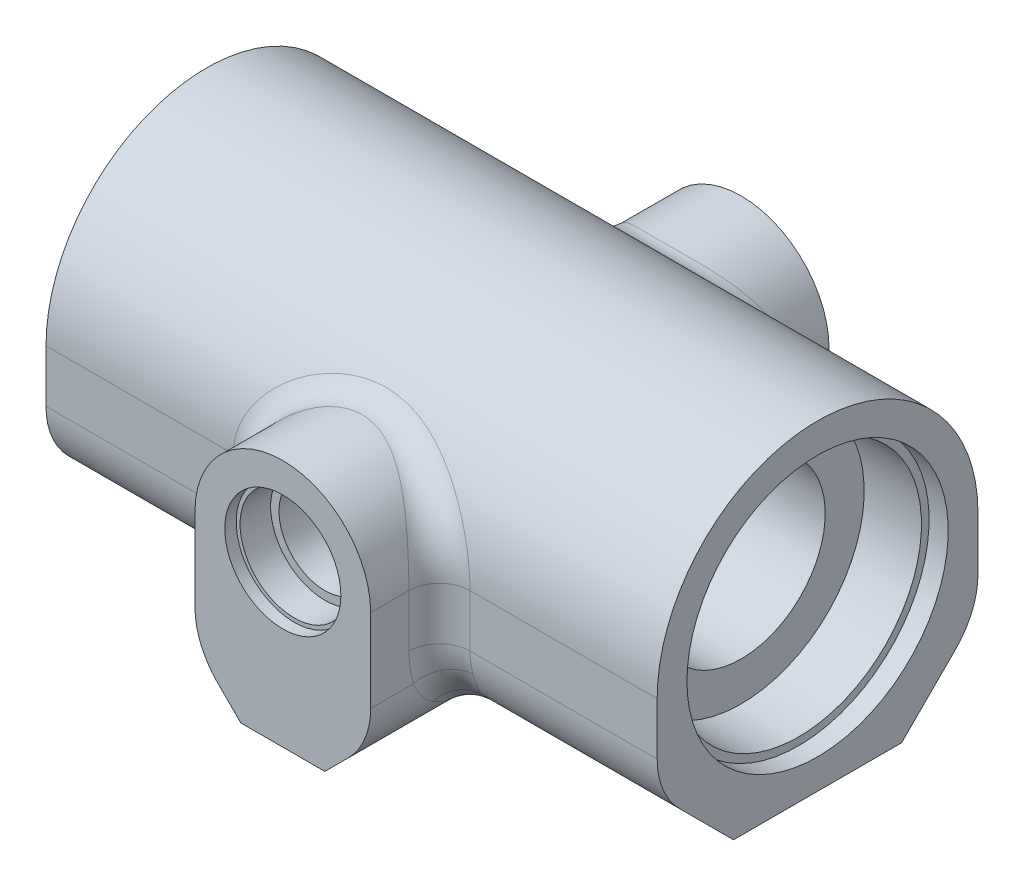
SolidWorks part; units mm, degrees
ref_plane "Front Plane" through (0, 0, 0) normal (0, 0, 1) x (1, 0, 0)
ref_plane "Top Plane" through (0, 0, 0) normal (0, 1, 0) x (1, 0, 0)
ref_plane "Right Plane" through (0, 0, 0) normal (1, 0, 0) x (0, 0, -1)
sketch "Sketch3" plane through (0, 0, 0) normal (1, 0, 0) x (0, 0, -1)
  line L3 (-21, 0) -> (-21, -21)
  line L4 (-21, -21) -> (21, -21)
  line L5 (21, -21) -> (21, 0)
  arc A1 (21, 0) -> (-21, 0) centre (0, 0) ccw
  arc A2 (-21, 0) -> (0, -21) centre (0, 0) ccw construction
  arc A3 (0, -21) -> (21, 0) centre (0, 0) ccw construction
  dimension "D1" = 42
extrude "Boss-Extrude1" add sketch "Sketch3" along normal mid plane 80
sketch "Sketch4" plane through (0, 0, 0) normal (0, 0, 1) x (1, 0, 0)
  line L0 (-11.5, 0) -> (-11.5, -21)
  line L1 (-11.5, -21) -> (11.5, -21)
  line L2 (11.5, -21) -> (11.5, 0)
  line L3 (0, 0) -> (26.2148, 0) construction
  arc A0 (11.5, 0) -> (-11.5, 0) centre (0, 0) ccw
  arc A1 (-11.5, 0) -> (11.5, 0) centre (0, 0) ccw construction
  dimension "D1" = 23
  dimension "D2" = 42
extrude "Boss-Extrude2" add sketch "Sketch4" along normal mid plane 60
chamfer "Chamfer1" distance 10 angle 45 4 edges at (25.75, -21, -21) (25.75, -21, 21) (-25.75, -21, -21) (-25.75, -21, 21)
fillet "Fillet1" radius 10 4 edges at (25.75, -11, 21) (25.75, -11, -21) (-25.75, -11, -21) (-25.75, -11, 21)
chamfer "Chamfer2" distance 6 angle 45 4 edges at (-11.5, -21, -20.5) (11.5, -21, -20.5) (-11.5, -21, 20.5) (11.5, -21, 20.5)
fillet "Fillet2" radius 10 4 edges at (-11.5, -15, 23.5) (11.5, -15, 23.5) (-11.5, -15, -23.5) (11.5, -15, -23.5)
fillet "Fillet3" radius 4 22 edges at (-7.0355, -19.4645, -12.5355) (-10.0316, -16.0743, -15.9257) (-11.191, -13.3244, -18.6279) (-11.5, -8.901, -20.7891) (7.0355, -19.4645, -12.5355) (10.0316, -16.0743, -15.9257) (11.4715, -11.6126, -19.7973) (11.5, -8.901, -20.7891) (11.5, -3.4289, -21) (0.6527, 11.4815, -17.5834) (7.0355, -19.4645, 12.5355) (10.0316, -16.0743, 15.9257) (11.191, -13.3244, 18.6279) (11.5, -8.901, 20.7891) (11.5, -3.4289, 21) (-7.0355, -19.4645, 12.5355) (-10.0316, -16.0743, 15.9257) (-11.4715, -11.6126, 19.7973) (-11.5, -8.901, 20.7891) (-11.5, -3.4289, 21) (-11.5, -3.4289, -21) (-0.6527, 11.4815, 17.5834)
sketch "Sketch5" plane through (0, 0, 0) normal (0, 0, 1) x (1, 0, 0)
  line L0 (0, 26.0006) -> (0, -28.8148) construction
  line L1 (0, 11) -> (30, 11)
  line L2 (30, 11) -> (30, 16.1)
  line L3 (30, 16.1) -> (37.5, 16.1)
  line L4 (37.5, 16.1) -> (37.5, 17.1)
  line L5 (37.5, 17.1) -> (40, 17.1)
  line L6 (40, 17.1) -> (40, 0)
  line L7 (40, 0) -> (0, 0)
  line L8 (-19.1793, 0) -> (44.5682, 0) construction
  line L9 (0, 11) -> (0, 0)
  dimension "D1" = 22
  dimension "D2" = 32.2
  dimension "D3" = 34.2
  dimension "D4" = 80
  dimension "D5" = 7.5
  dimension "D6" = 2.5
revolve "Cut-Revolve1" cut sketch "Sketch5" angle 360 about L8
mirror "Mirror2" about plane through (0, 0, 0) normal (1, 0, 0) of "Cut-Revolve1"
sketch "Sketch6" plane through (0, 0, 0) normal (1, 0, 0) x (0, 0, -1)
  line L0 (0, 30.2875) -> (0, -30.2875) construction
  line L1 (-33.8158, 0) -> (41.0309, 0) construction
  line L2 (0, 0) -> (30, 0)
  line L3 (30, 0) -> (30, 7.6)
  line L4 (30, 7.6) -> (28.5, 7.6)
  line L5 (28.5, 7.6) -> (28.5, 7.1)
  line L6 (28.5, 7.1) -> (24.5, 7.1)
  line L7 (24.5, 7.1) -> (24.5, 6)
  line L8 (24.5, 6) -> (0, 6)
  line L9 (0, 6) -> (0, 0)
  dimension "D1" = 60
  dimension "D2" = 12
  dimension "D3" = 15.2
  dimension "D4" = 14.2
  dimension "D5" = 1.5
  dimension "D6" = 4
revolve "Cut-Revolve2" cut sketch "Sketch6" angle 360 about L1
mirror "Mirror3" about plane through (0, 0, 0) normal (0, 0, 1) of "Cut-Revolve2"
equation "\"length\"= 80mm"
equation "\"width\"= 60mm"
equation "\"D1@Boss-Extrude1\"=\"length\""
equation "\"D1@Boss-Extrude2\"=\"width\""
equation "\"D4@Sketch5\"=\"length\""
equation "\"D1@Sketch6\"=\"width\""
